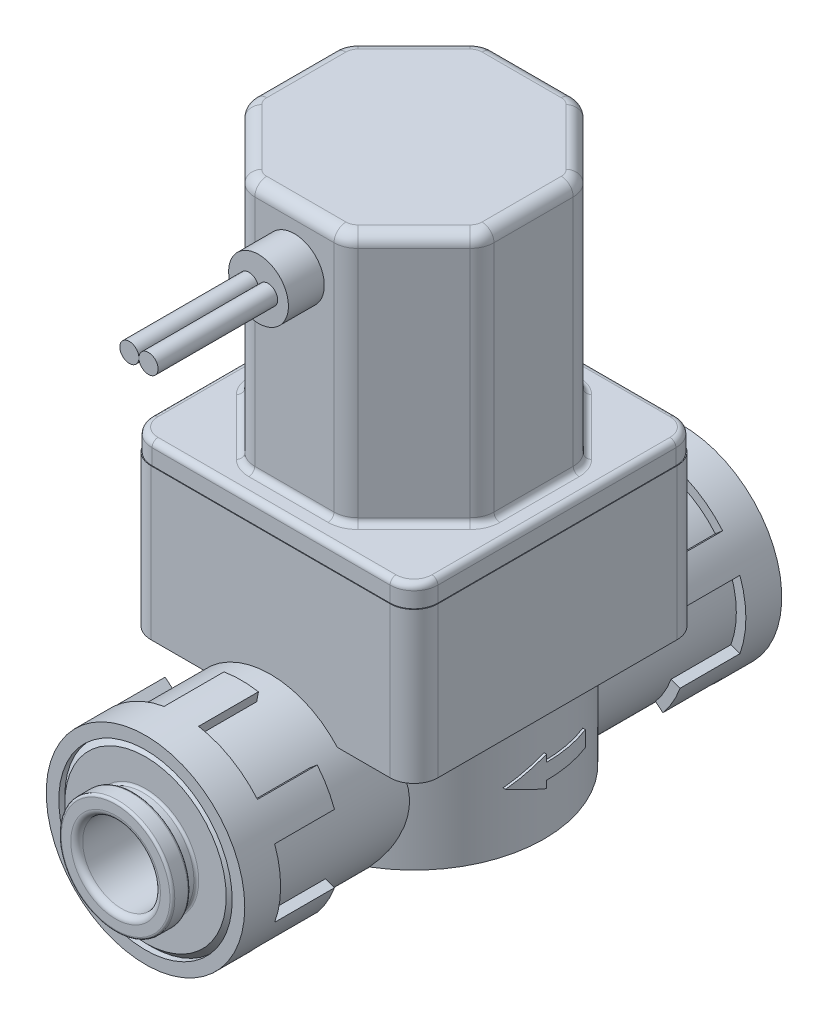
SolidWorks part; units mm, degrees
material "POM copolymère d'acétal"
ref_plane "Plan de face" through (0, 0, 0) normal (0, 0, 1) x (1, 0, 0)
ref_plane "Plan de dessus" through (0, 0, 0) normal (0, 1, 0) x (1, 0, 0)
ref_plane "Plan de droite" through (0, 0, 0) normal (1, 0, 0) x (0, 0, -1)
sketch "Esquisse1" plane through (0, 0, 0) normal (1, 0, 0) x (0, 0, -1)
  line L0 (-5.9952, 0) -> (9.4709, 0) construction
  line L1 (-24.45, 3.25) -> (-10.45, 3.25)
  line L2 (-10.45, 4.7625) -> (-10.75, 4.7625)
  line L3 (-10.95, 4.9625) -> (-10.95, 5.7)
  line L4 (-11.95, 6.7) -> (-11.9577, 6.7)
  line L5 (-12.95, 6.7) -> (-12.95, 6.75)
  line L6 (-13.45, 7.25) -> (-21.95, 7.25)
  line L7 (-22.45, 6.75) -> (-22.45, 4.45)
  line L8 (-22.65, 4.25) -> (-23.25, 4.25)
  line L9 (-23.45, 4.45) -> (-23.45, 4.55)
  line L10 (-23.65, 4.75) -> (-24.75, 4.75)
  line L11 (-24.95, 4.55) -> (-24.95, 3.75)
  line L12 (-10.45, 4.7625) -> (-10.45, 3.25)
  line L13 (-10.95, 5.7) -> (-11.95, 6.7)
  line L14 (-12.95, 6.75) -> (-13.45, 7.25)
  line L15 (-21.95, 7.25) -> (-22.45, 6.75)
  line L16 (-12.95, 6.7) -> (-11.9577, 6.7)
  arc A0 (-10.75, 4.7625) -> (-10.95, 4.9625) centre (-10.75, 4.9625) cw
  arc A2 (-22.45, 4.45) -> (-22.65, 4.25) centre (-22.65, 4.45) cw
  arc A3 (-23.25, 4.25) -> (-23.45, 4.45) centre (-23.25, 4.45) cw
  arc A4 (-23.45, 4.55) -> (-23.65, 4.75) centre (-23.65, 4.55) ccw
  arc A5 (-24.75, 4.75) -> (-24.95, 4.55) centre (-24.75, 4.55) ccw
  arc A6 (-24.45, 3.25) -> (-24.95, 3.75) centre (-24.45, 3.75) cw
  point P5 (-22.45, 7.25)
  point P8 (-10.95, 6.7)
  point P9 (-9.8276, 6.7)
  point P10 (-12.95, 7.25)
  point P11 (-24.2, 4.75)
  point P16 (-23.45, 4.5)
  point P17 (-10.45, 4.0063)
  point P18 (0, 0)
  point P39 (-11.9577, 6.7)
  point P40 (-11.9577, 6.7)
  dimension "D12" = 0.2
  dimension "D13" = 0.5
  dimension "D1" = 9.5
  dimension "D2" = 6.5
  dimension "D3" = 8.5
  dimension "D4" = 14.5
  dimension "D5" = 9.5
  dimension "D6" = 1
  dimension "D7" = 1.5
  dimension "D8" = 9.525
  dimension "D9" = 13.4
  dimension "D10" = 2
  dimension "D11" = 0.5
  dimension "D14" = 22.45
revolve "Révolution1" add sketch "Esquisse1" angle 360 about L0
sketch "Esquisse2" plane through (0, 0, 0) normal (1, 0, 0) x (0, 0, -1)
  line L0 (0, 12.6848) -> (0, -12.6848) construction
sketch "Esquisse3" plane through (0, 0, 22.45) normal (0, 0, 1) x (1, 0, 0)
  circle A0 centre (0, 0) radius 7.25
  circle A1 centre (0, 0) radius 8.3
  dimension "D1" = 16.6
extrude "Boss.-Extru.1" add sketch "Esquisse3" against normal blind 3
sketch "Esquisse4" plane through (0, 0, 19.45) normal (0, 0, -1) x (-1, 0, 0)
  line L0 (-1.2589, 7.1399) -> (0, 0) construction
  line L1 (0, 0) -> (1.2589, 7.1399) construction
  line L2 (-1.4413, 8.1739) -> (-1.2589, 7.1399)
  line L3 (1.4413, 8.1739) -> (1.2589, 7.1399)
  line L7 (7.7994, 2.8388) -> (6.8128, 2.4796)
  line L8 (6.3582, 5.3351) -> (5.5538, 4.6602)
  line L9 (6.3582, -5.3351) -> (5.5538, -4.6602)
  line L10 (7.7994, -2.8388) -> (6.8128, -2.4796)
  line L11 (-1.4413, -8.1739) -> (-1.2589, -7.1399)
  line L12 (1.4413, -8.1739) -> (1.2589, -7.1399)
  line L13 (-7.7994, -2.8388) -> (-6.8128, -2.4796)
  line L14 (-6.3582, -5.3351) -> (-5.5538, -4.6602)
  line L15 (-6.3582, 5.3351) -> (-5.5538, 4.6602)
  line L16 (-7.7994, 2.8388) -> (-6.8128, 2.4796)
  arc A0 (-1.2589, 7.1399) -> (1.2589, 7.1399) centre (0, 0) cw
  circle A1 centre (0, 0) radius 7.25 construction
  arc A2 (-1.4413, 8.1739) -> (1.4413, 8.1739) centre (0, 0) cw
  circle A3 centre (0, 0) radius 8.3 construction
  arc A4 (5.5538, 4.6602) -> (6.8128, 2.4796) centre (0, 0) cw
  arc A5 (6.3582, 5.3351) -> (7.7994, 2.8388) centre (0, 0) cw
  arc A6 (6.8128, -2.4796) -> (5.5538, -4.6602) centre (0, 0) cw
  arc A7 (7.7994, -2.8388) -> (6.3582, -5.3351) centre (0, 0) cw
  arc A8 (1.2589, -7.1399) -> (-1.2589, -7.1399) centre (0, 0) cw
  arc A9 (1.4413, -8.1739) -> (-1.4413, -8.1739) centre (0, 0) cw
  arc A10 (-5.5538, -4.6602) -> (-6.8128, -2.4796) centre (0, 0) cw
  arc A11 (-6.3582, -5.3351) -> (-7.7994, -2.8388) centre (0, 0) cw
  arc A12 (-6.8128, 2.4796) -> (-5.5538, 4.6602) centre (0, 0) cw
  arc A13 (-7.7994, 2.8388) -> (-6.3582, 5.3351) centre (0, 0) cw
  point P12 (0, 7.25)
  dimension "D1" = 20
  dimension "D2" = 6
extrude "Boss.-Extru.2" add sketch "Esquisse4" along normal blind 5
pattern_circular "Répétition circulaire5" count 2 over 360 about axis through (0, 12.6848, 0) along (0, -1, 0) of bodies 114
sketch "Esquisse5" plane through (0, 0, 19.45) normal (0, 0, -1) x (-1, 0, 0)
  circle A0 centre (0, 0) radius 7.25
  circle A1 centre (0, 0) radius 7.5
  dimension "D1" = 15
extrude "Boss.-Extru.3" add sketch "Esquisse5" along normal up to next
sketch "Esquisse7" plane through (0, 0, 0) normal (0, 1, 0) x (1, 0, 0)
  circle A0 centre (0, 0) radius 10.875
  dimension "D1" = 21.75
extrude "Boss.-Extru.4" add sketch "Esquisse7" along normal blind 5 and the other way blind 5
sketch "Esquisse8" plane through (0, 5, 0) normal (0, 1, 0) x (1, 0, 0)
  line L1 (-10, 12) -> (10, 12)
  line L2 (-12, 10) -> (-12, -10)
  line L3 (-10, -12) -> (10, -12)
  line L4 (12, 10) -> (12, -10)
  line L5 (-12, 12) -> (12, -12) construction
  line L6 (-12, -12) -> (12, 12) construction
  arc A0 (-10, 12) -> (-12, 10) centre (-10, 10) ccw
  arc A1 (-12, -10) -> (-10, -12) centre (-10, -10) ccw
  arc A2 (10, -12) -> (12, -10) centre (10, -10) ccw
  arc A3 (10, 12) -> (12, 10) centre (10, 10) cw
  point P0 (0, 0)
  dimension "D3" = 2
  dimension "D1" = 24
  dimension "D2" = 24
extrude "Boss.-Extru.5" add sketch "Esquisse8" along normal blind 12.6
sketch "Esquisse11" plane through (0, 0, 0) normal (1, 0, 0) x (0, 0, -1)
  line L1 (0, -1.25) -> (-3, 0)
  line L2 (-3, 0) -> (0, 1.25)
  line L3 (4, 0.65) -> (0, 0.65)
  line L5 (0, -0.65) -> (4, -0.65)
  line L6 (4, -0.65) -> (4, 0.65)
  line L7 (0, 1.25) -> (0, 0.65)
  line L8 (0, -0.65) -> (0, -1.25)
  line L9 (0, 0.65) -> (0, -0.65) construction
  line L10 (-3, 0) -> (4, 0) construction
  point P2 (0, 0)
  dimension "D1" = 1.3
  dimension "D2" = 3
  dimension "D3" = 4
  dimension "D4" = 2.5
extrude "Boss.-Extru.8" add sketch "Esquisse11" along normal blind 11.5 and the other way blind 11.5
sketch "Esquisse12" plane through (0, -5, 0) normal (0, -1, 0) x (1, 0, 0)
  line L0 (-11.5492, 5.9678) -> (-9.7976, 5.1635)
  line L1 (-9.1058, -6.3039) -> (-10.7299, -7.3396)
  line L2 (9.1058, 6.3039) -> (10.7299, 7.3396)
  line L3 (11.5492, -5.9678) -> (9.7976, -5.1635)
  arc A2 (-9.1058, -6.3039) -> (-9.7976, 5.1635) centre (0, 0) cw
  arc A3 (-10.7299, -7.3396) -> (-11.5492, 5.9678) centre (0, 0) cw
  arc A4 (-5.5902, 9.3282) -> (-5.5902, -9.3282) centre (0, 0) ccw construction
  arc A5 (10.7299, 7.3396) -> (11.5492, -5.9678) centre (0, 0) cw
  arc A6 (9.1058, 6.3039) -> (9.7976, -5.1635) centre (0, 0) cw
  dimension "D1" = 0.2
  dimension "D2" = 13
  dimension "D3" = 2
extrude "Enlèv. mat.-Extru.1" cut sketch "Esquisse12" against normal up to next
sketch "Esquisse9" plane through (0, 17.6, 0) normal (0, 1, 0) x (1, 0, 0)
  line L1 (-9.95, -11.95) -> (9.95, -11.95)
  line L2 (-11.95, -9.95) -> (-11.95, 9.95)
  line L3 (-9.95, 11.95) -> (9.95, 11.95)
  line L4 (11.95, -9.95) -> (11.95, 9.95)
  line L5 (-11.95, -11.95) -> (11.95, 11.95) construction
  line L6 (-11.95, 11.95) -> (11.95, -11.95) construction
  arc A0 (-9.95, -11.95) -> (-11.95, -9.95) centre (-9.95, -9.95) cw
  arc A1 (9.95, -11.95) -> (11.95, -9.95) centre (9.95, -9.95) ccw
  arc A2 (9.95, 11.95) -> (11.95, 9.95) centre (9.95, 9.95) cw
  arc A3 (-11.95, 9.95) -> (-9.95, 11.95) centre (-9.95, 9.95) cw
  point P0 (0, 0)
  dimension "D1" = 2
  dimension "D2" = 23.9
  dimension "D3" = 23.9
extrude "Boss.-Extru.6" add sketch "Esquisse9" along normal blind 1.8
sketch "Esquisse10" plane through (0, 19.4, 0) normal (0, 1, 0) x (1, 0, 0)
  line L0 (-3.3137, -10) -> (3.3137, -10)
  line L1 (10, -3.3137) -> (10, 3.3137)
  line L2 (9.4142, 4.7279) -> (4.7279, 9.4142)
  line L3 (3.3137, 10) -> (-3.3137, 10)
  line L4 (-4.7279, 9.4142) -> (-9.4142, 4.7279)
  line L5 (-10, 3.3137) -> (-10, -3.3137)
  line L6 (-9.4142, -4.7279) -> (-4.7279, -9.4142)
  line L7 (4.7279, -9.4142) -> (9.4142, -4.7279)
  line L8 (9.95, 11.95) -> (-9.95, 11.95) construction
  circle A0 centre (0, 0) radius 10 construction
  arc A1 (4.7279, 9.4142) -> (3.3137, 10) centre (3.3137, 8) ccw
  arc A2 (10, 3.3137) -> (9.4142, 4.7279) centre (8, 3.3137) ccw
  arc A3 (10, -3.3137) -> (9.4142, -4.7279) centre (8, -3.3137) cw
  arc A4 (3.3137, -10) -> (4.7279, -9.4142) centre (3.3137, -8) ccw
  arc A5 (-4.7279, -9.4142) -> (-3.3137, -10) centre (-3.3137, -8) ccw
  arc A6 (-10, -3.3137) -> (-9.4142, -4.7279) centre (-8, -3.3137) ccw
  arc A7 (-9.4142, 4.7279) -> (-10, 3.3137) centre (-8, 3.3137) ccw
  arc A8 (-3.3137, 10) -> (-4.7279, 9.4142) centre (-3.3137, 8) ccw
  dimension "D2" = 2
  dimension "D1" = 20
extrude "Boss.-Extru.7" add sketch "Esquisse10" along normal blind 21
fillet "Congé2" radius 0.5 24 edges at (-11.3642, 19.4, -11.3642) (0, 19.4, -11.95) (11.3642, 19.4, -11.3642) (11.95, 19.4, 0) (11.3642, 19.4, 11.3642) (0, 19.4, 11.95) (-11.3642, 19.4, 11.3642) (-4.0791, 19.4, -9.8478) (0, 19.4, -10) (4.0791, 19.4, -9.8478) (7.0711, 19.4, -7.0711) (9.8478, 19.4, -4.0791) (10, 19.4, 0) (9.8478, 19.4, 4.0791) (7.0711, 19.4, 7.0711) (4.0791, 19.4, 9.8478) (0, 19.4, 10) (-4.0791, 19.4, 9.8478) (-7.0711, 19.4, 7.0711) (-9.8478, 19.4, 4.0791) (-10, 19.4, 0) (-9.8478, 19.4, -4.0791) (-11.95, 19.4, 0) (-7.0711, 19.4, -7.0711)
fillet "Congé3" radius 1 16 edges at (-4.0791, 40.4, -9.8478) (0, 40.4, -10) (4.0791, 40.4, -9.8478) (7.0711, 40.4, -7.0711) (9.8478, 40.4, -4.0791) (10, 40.4, 0) (9.8478, 40.4, 4.0791) (7.0711, 40.4, 7.0711) (4.0791, 40.4, 9.8478) (0, 40.4, 10) (-4.0791, 40.4, 9.8478) (-7.0711, 40.4, 7.0711) (-9.8478, 40.4, 4.0791) (-10, 40.4, 0) (-9.8478, 40.4, -4.0791) (-7.0711, 40.4, -7.0711)
sketch "Esquisse13" plane through (0, 0, 10) normal (0, 0, 1) x (1, 0, 0)
  line L0 (-3.3137, 35.9) -> (3.3137, 35.9) construction
  line L1 (-3.3137, 39.4) -> (-3.3137, 19.9) construction
  line L2 (3.3137, 39.4) -> (3.3137, 19.9) construction
  line L3 (3.3137, 35.9) -> (3.3137, 19.9) construction
  circle A0 centre (0, 35.9) radius 2.5
  point P2 (-0.8802, 35.5032)
  point P11 (0, 35.9)
  dimension "D1" = 16
extrude "Boss.-Extru.9" add sketch "Esquisse13" along normal blind 3
sketch "Esquisse14" plane through (0, 0, 13) normal (0, 0, 1) x (1, 0, 0)
  line L0 (-0.8, 35.9) -> (0.8, 35.9) construction
  circle A0 centre (-0.8, 35.9) radius 0.8
  circle A1 centre (0.8, 35.9) radius 0.8
  point P4 (0, 35.9)
  point P5 (0, 35.9)
  dimension "D1" = 1.6
extrude "Boss.-Extru.11" add sketch "Esquisse14" along normal blind 10 separate body contours A0 | A1 region at (-0.8, 35.9, 13) region at (0.8, 35.9, 13)
